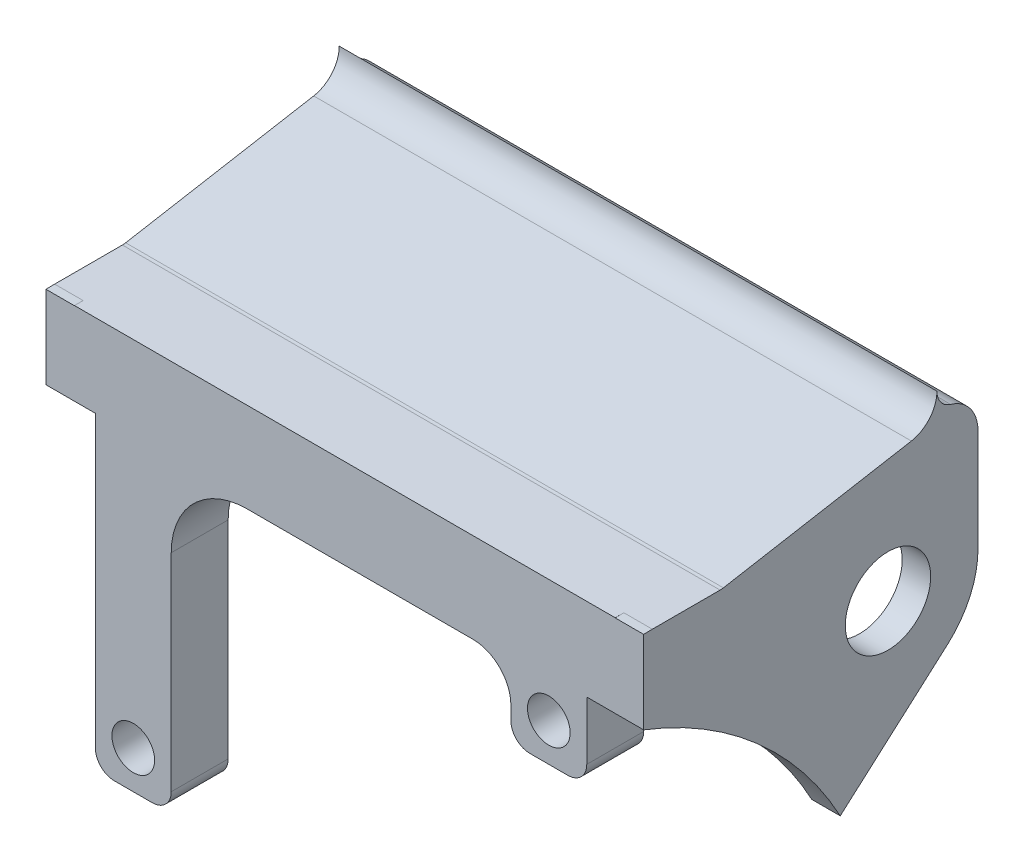
SolidWorks part; units mm, degrees
ref_plane "Front Plane" through (0, 0, 0) normal (0, 0, 1) x (1, 0, 0)
ref_plane "Top Plane" through (0, 0, 0) normal (0, 1, 0) x (1, 0, 0)
ref_plane "Right Plane" through (0, 0, 0) normal (1, 0, 0) x (0, 0, -1)
sketch "Sketch1" plane through (0, 0, 0) normal (0, 0, 1) x (1, 0, 0)
  line L0 (-13.15, 3.3278) -> (-13.15, -13.8717)
  line L1 (-12.15, -14.8717) -> (-10.15, -14.8717)
  line L2 (-9.15, -13.8717) -> (-9.15, -2.9618)
  line L3 (-5.15, 1.0382) -> (6.75, 1.0382)
  line L4 (8.75, -0.9618) -> (8.75, -1.6717)
  line L5 (9.75, -2.6717) -> (11.75, -2.6717)
  line L6 (12.75, -1.6717) -> (12.75, 3.3278)
  line L7 (12.75, 3.3278) -> (-13.15, 3.3278)
  circle A0 centre (-11.15, -12.8717) radius 1.125
  circle A1 centre (10.75, -0.6717) radius 1.125
  arc A2 (11.75, -2.6717) -> (12.75, -1.6717) centre (11.75, -1.6717) ccw
  arc A3 (8.75, -1.6717) -> (9.75, -2.6717) centre (9.75, -1.6717) ccw
  arc A4 (-10.15, -14.8717) -> (-9.15, -13.8717) centre (-10.15, -13.8717) ccw
  arc A5 (-13.15, -13.8717) -> (-12.15, -14.8717) centre (-12.15, -13.8717) ccw
  arc A6 (-9.15, -2.9618) -> (-5.15, 1.0382) centre (-5.15, -2.9618) cw
  arc A7 (6.75, 1.0382) -> (8.75, -0.9618) centre (6.75, -0.9618) cw
  dimension "D1" = 2.25
  dimension "D2" = 2
  dimension "D3" = 2
  dimension "D4" = 2
  dimension "D5" = 2.25
  dimension "D6" = 2
  dimension "D7" = 2
  dimension "D8" = 2
  dimension "D9" = 21.9
  dimension "D10" = 1
  dimension "D11" = 4
  dimension "D12" = 2
  dimension "D13" = 12.2
  dimension "D14" = 9.15
extrude "Boss-Extrude1" add sketch "Sketch1" along normal blind 3
sketch "Sketch2" plane through (12.75, 0, 0) normal (1, 0, 0) x (0, 0, -1)
  line L0 (-3, -1.6717) -> (-3, 3.3278) construction
  line L2 (0, -1.6717) -> (0, 3.3278) construction
  line L4 (0, -1.6717) -> (0, 3.3278)
  line L5 (0, 3.3278) -> (-3, 3.3278)
  line L6 (-3, 3.3278) -> (-3, -1.6717)
  line L7 (-3, -1.6717) -> (0, -1.6717)
  line L8 (0, -0.0484) -> (0, 3.3278)
  line L9 (0, 3.3278) -> (-3, 3.3278)
  line L10 (-3, 3.3278) -> (-3, 1.4031)
  arc A0 (7.3599, -7.7028) -> (-20.2974, -34.2208) centre (-10.1246, -17.1489) ccw construction
  arc A1 (0, -0.0484) -> (-3, 1.4031) centre (-10.1246, -17.1489) ccw
  dimension "D1" = 0
extrude "Boss-Extrude2" add sketch "Sketch2" along normal up to surface (3 mm away) separate body
sketch "Sketch4" plane through (15.75, 0, 0) normal (-1, 0, 0) x (0, 0, 1)
  line L3 (-14.6194, 0.8511) -> (-14.6194, 6.2511) construction
  line L7 (-14.6194, 0.8511) -> (-14.6194, 6.2511)
  line L8 (2.5446, 5.7711) -> (-1.0254, 5.7711) construction
  line L11 (-11.1085, 7.5336) -> (-1.199, 5.7863) construction
  line L13 (-7.3599, -7.7028) -> (-13.0168, -2.7037) construction
  line L15 (-7.3599, -7.7028) -> (-13.0168, -2.7037)
  line L18 (3, 1.4031) -> (3, 3.3278) construction
  line L19 (3, 5.7632) -> (3, 1.4031)
  line L20 (2.5446, 5.7711) -> (-1.0254, 5.7711)
  line L21 (-11.1085, 7.5336) -> (-1.199, 5.7863)
  line L22 (2.5446, 5.7711) -> (12.59, 5.5974) construction
  line L23 (2.5446, 5.7711) -> (3, 5.7632)
  arc A0 (-13.1767, 8.1719) -> (-12.4554, 9.1347) centre (-13.4554, 9.1322) ccw construction
  arc A2 (-13.1767, 8.1719) -> (-12.4554, 9.1347) centre (-13.4554, 9.1322) ccw
  arc A5 (-13.1767, 8.1719) -> (-14.6194, 6.2511) centre (-12.6194, 6.2511) ccw construction
  arc A7 (-14.6194, 0.8511) -> (-13.0168, -2.7037) centre (-9.8754, 0.8511) ccw construction
  arc A8 (20.2974, -34.2208) -> (-7.3599, -7.7028) centre (10.1246, -17.1489) ccw construction
  arc A9 (-14.6194, 0.8511) -> (-13.0168, -2.7037) centre (-9.8754, 0.8511) ccw
  arc A10 (3, 1.4031) -> (-7.3599, -7.7028) centre (10.1246, -17.1489) ccw
  circle A11 centre (-9.8754, 0.8511) radius 2.25 construction
  circle A12 centre (-9.8754, 0.8511) radius 2.25
  arc A13 (-13.1767, 8.1719) -> (-14.6194, 6.2511) centre (-12.6194, 6.2511) ccw
  arc A14 (-12.4554, 9.1347) -> (-11.1085, 7.5336) centre (-10.8254, 9.1388) ccw construction
  arc A15 (-12.4554, 9.1347) -> (-11.1085, 7.5336) centre (-10.8254, 9.1388) ccw
  arc A16 (-1.199, 5.7863) -> (-1.0254, 5.7711) centre (-1.0254, 6.7711) ccw construction
  arc A17 (-1.199, 5.7863) -> (-1.0254, 5.7711) centre (-1.0254, 6.7711) ccw
extrude "Boss-Extrude4" add sketch "Sketch4" along normal blind 1.5
mirror "Mirror4" about plane through (0, 0, 0) normal (1, 0, 0) of "Boss-Extrude4", "Boss-Extrude2"
sketch "Sketch5" plane through (14.25, 0, 0) normal (-1, 0, 0) x (0, 0, 1)
  line L1 (-14.6194, 6.2511) -> (-14.6194, 0.8511) construction
  line L6 (-14.6194, 6.2511) -> (-14.6194, 0.8511) construction
  line L8 (0, 5.7711) -> (0, 4.9111)
  line L10 (-1.199, 5.7863) -> (-11.1085, 7.5336) construction
  line L12 (-14.6194, 5.4111) -> (-14.6194, 6.2511)
  line L13 (-14.1194, 4.9111) -> (0, 4.9111)
  line L14 (-1.199, 5.7863) -> (-11.1085, 7.5336)
  line L15 (2.5446, 5.7711) -> (-1.0254, 5.7711) construction
  line L16 (0, 5.7711) -> (-1.0254, 5.7711)
  arc A0 (-13.1767, 8.1719) -> (-14.6194, 6.2511) centre (-12.6194, 6.2511) ccw construction
  arc A1 (-13.1767, 8.1719) -> (-12.4554, 9.1347) centre (-13.4554, 9.1322) ccw construction
  arc A2 (-13.1767, 8.1719) -> (-14.6194, 6.2511) centre (-12.6194, 6.2511) ccw
  arc A3 (-13.1767, 8.1719) -> (-12.4554, 9.1347) centre (-13.4554, 9.1322) ccw
  arc A4 (-14.6194, 5.4111) -> (-14.1194, 4.9111) centre (-14.1194, 5.4111) ccw
  arc A5 (-12.4554, 9.1347) -> (-11.1085, 7.5336) centre (-10.8254, 9.1388) ccw construction
  arc A6 (-12.4554, 9.1347) -> (-11.1085, 7.5336) centre (-10.8254, 9.1388) ccw
  arc A7 (-1.199, 5.7863) -> (-1.0254, 5.7711) centre (-1.0254, 6.7711) ccw construction
  arc A8 (-1.199, 5.7863) -> (-1.0254, 5.7711) centre (-1.0254, 6.7711) ccw
  point P24 (-14.6194, 4.9111)
  dimension "D2" = 0.5
extrude "Boss-Extrude5" add sketch "Sketch5" along normal up to surface (28.5 mm away)
sketch "Sketch8" plane through (0, 3.3278, 0) normal (0, 1, 0) x (1, 0, 0)
  line L24 (-14.25, 0) -> (14.25, 0)
  line L25 (-14.25, 0) -> (-14.25, -3)
  line L26 (-14.25, -3) -> (14.25, -3)
  line L27 (14.25, 0) -> (14.25, -3)
extrude "Boss-Extrude13" add sketch "Sketch8" along normal up to surface (2.4433 mm away) up to face at (-15, 5.7711, 0.7596)
fillet "Fillet1" radius 2 1 edges at (0, 4.9111, 0)
fillet "Fillet2" radius 1 2 edges at (-14.25, 1.4314, 0) (14.25, 1.4314, 0)
